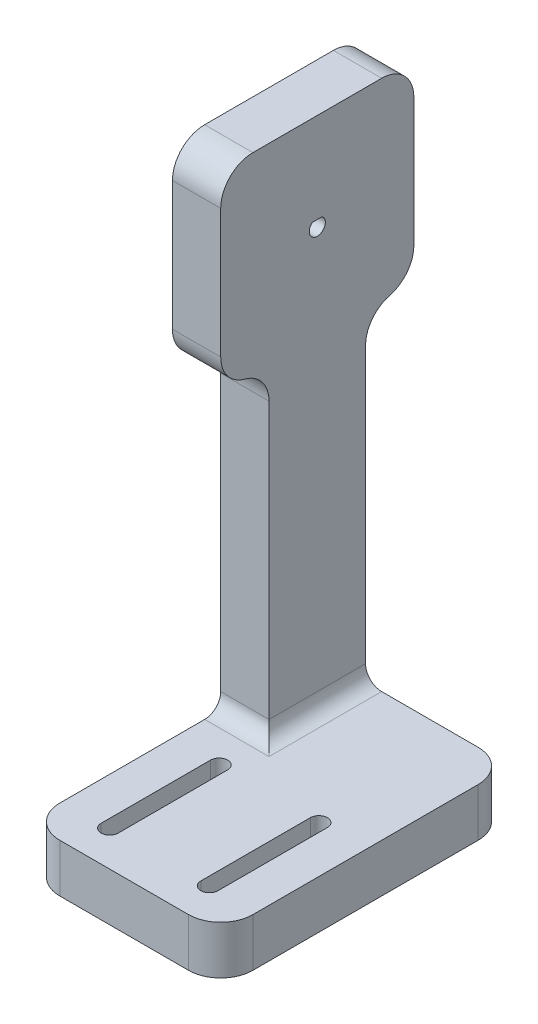
SolidWorks part; units mm, degrees
ref_plane "Front Plane" through (0, 0, 0) normal (0, 0, 1) x (1, 0, 0)
ref_plane "Top Plane" through (0, 0, 0) normal (0, 1, 0) x (1, 0, 0)
ref_plane "Right Plane" through (0, 0, 0) normal (1, 0, 0) x (0, 0, -1)
sketch "Sketch1" plane through (0, 0, 0) normal (1, 0, 0) x (0, 0, -1)
  line L1 (30, -30) -> (-30, -30)
  line L2 (30, -30) -> (30, 30)
  line L3 (30, 30) -> (-30, 30)
  line L4 (-30, -30) -> (-30, 30)
  line L5 (30, -30) -> (-30, 30) construction
  line L6 (30, 30) -> (-30, -30) construction
  point P0 (0, 0)
  dimension "D1" = 60
  dimension "D2" = 60
extrude "Boss-Extrude1" add sketch "Sketch1" along normal blind 15
sketch "Sketch2" plane through (15, 0, 0) normal (1, 0, 0) x (0, 0, -1)
  line L0 (0, 0) -> (0, 30) construction
  line L1 (30, 30) -> (-30, 30) construction
  line L2 (1.5, 2) -> (-1.5, 2)
  circle A0 centre (0, 0) radius 2.5
  dimension "D1" = 5
  dimension "D2" = 3
extrude "Cut-Extrude1" cut sketch "Sketch2" against normal up to surface (15 mm away) contours A0 region at (15, -0.1209, 0) up to face at (0, 0, 0)
sketch "Sketch8" plane through (0, -30, 0) normal (0, -1, 0) x (1, 0, 0)
  line L0 (0, 30) -> (0, 15) construction
  line L1 (0, 30) -> (0, -30) construction
  line L2 (15, 30) -> (15, -30) construction
  line L3 (0, 15) -> (15, 15)
  line L4 (0, 15) -> (0, -15)
  line L5 (0, -15) -> (15, -15)
  line L6 (15, 15) -> (15, -15)
  line L7 (0, -15) -> (0, -30) construction
  dimension "D1" = 30
extrude "Boss-Extrude2" add sketch "Sketch8" along normal blind 100
sketch "Sketch9" plane through (0, -130, 0) normal (0, -1, 0) x (1, 0, 0)
  line L0 (0, 0) -> (0, 75)
  line L1 (0, 15) -> (0, -15) construction
  line L2 (0, 75) -> (60, 75)
  line L3 (60, 75) -> (60, -15)
  line L4 (60, -15) -> (0, -15)
  line L5 (0, -15) -> (0, 0)
  dimension "D1" = 75
  dimension "D2" = 60
  dimension "D3" = 15
extrude "Boss-Extrude3" add sketch "Sketch9" along normal blind 15
sketch "Sketch10" plane through (0, -130, 0) normal (0, 1, 0) x (1, 0, 0)
  line L0 (60, -75) -> (42.85, -75) construction
  line L1 (60, -75) -> (0, -75) construction
  line L2 (42.85, -75) -> (17.15, -75) construction
  line L3 (17.15, -75) -> (0, -75) construction
  line L4 (42.85, -75) -> (42.85, -64) construction
  line L5 (42.85, -64) -> (45.5, -64) construction
  line L6 (48.15, -64) -> (48.15, -30)
  line L7 (42.85, -64) -> (42.85, -30)
  line L8 (42.85, -47) -> (48.15, -47) construction
  line L9 (30, -75) -> (30, -40.6705) construction
  line L10 (17.15, -64) -> (17.15, -30)
  line L11 (11.85, -64) -> (11.85, -30)
  arc A0 (42.85, -64) -> (48.15, -64) centre (45.5, -64) ccw
  arc A1 (42.85, -30) -> (48.15, -30) centre (45.5, -30) cw
  arc A2 (17.15, -30) -> (11.85, -30) centre (14.5, -30) ccw
  arc A3 (17.15, -64) -> (11.85, -64) centre (14.5, -64) cw
  dimension "D1" = 25.7
  dimension "D2" = 11
  dimension "D3" = 2.65
  dimension "D4" = 34
extrude "Cut-Extrude4" cut sketch "Sketch10" against normal up to surface (15 mm away) up to face at (30, -145, 30)
fillet "Fillet1" radius 10 4 edges at (7.5, 30, 30) (7.5, -30, 30) (7.5, -30, -30) (7.5, 30, -30)
fillet "Fillet2" radius 10 2 edges at (7.5, -30, 15) (7.5, -30, -15)
fillet "Fillet3" radius 5 2 edges at (7.5, -130, 15) (15, -130, 0)
fillet "Fillet4" radius 10 3 edges at (60, -137.5, 75) (0, -137.5, 75) (60, -137.5, -15)
